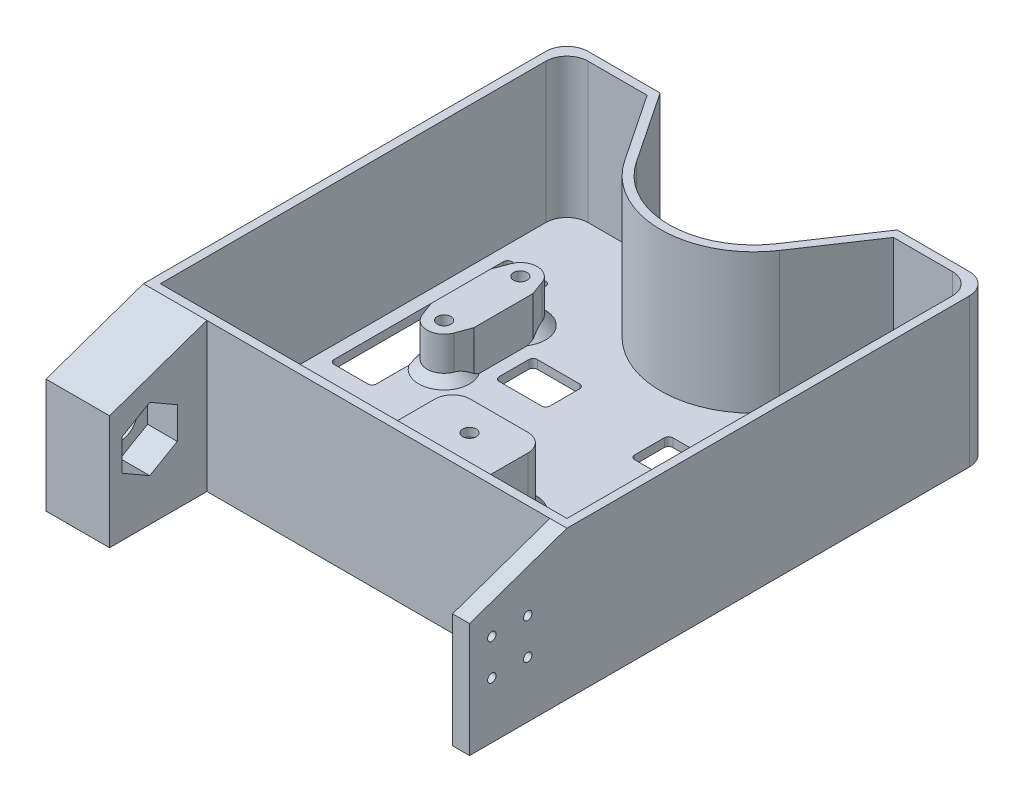
SolidWorks part; units mm, degrees
ref_plane "Ebene vorne" through (0, 0, 0) normal (0, 0, 1) x (1, 0, 0)
ref_plane "Ebene oben" through (0, 0, 0) normal (0, 1, 0) x (1, 0, 0)
ref_plane "Ebene rechts" through (0, 0, 0) normal (1, 0, 0) x (0, 0, -1)
sketch "Grundplatte" plane through (0, 0, 0) normal (0, 1, 0) x (1, 0, 0)
  line L0 (0, 69.0751) -> (0, -94.5087) construction
  line L2 (-50, 50) -> (-50, -50)
  line L3 (-50, -50) -> (50, -50)
  line L4 (50, 50) -> (50, -50)
  line L5 (-50, 50) -> (50, -50) construction
  line L6 (-50, -50) -> (50, 50) construction
  line L7 (-50, 50) -> (-28, 50)
  line L8 (-28, 50) -> (-16.6199, 33)
  line L9 (28, 50) -> (16.6199, 33)
  line L10 (50, 50) -> (28, 50)
  arc A0 (-16.6199, 33) -> (16.6199, 33) centre (0, 44.1257) ccw
  point P0 (0, 0)
  dimension "D4" = 20
  dimension "D1" = 100
  dimension "D2" = 100
  dimension "D3" = 22
  dimension "D5" = 17
extrude "Aufsatz-Linear austragen1" add sketch "Grundplatte" along normal blind 35
shell "Wandung1" thickness 2 removed face at (0, 35, -19.6407)
sketch "Skizze1" plane through (0, 2, 0) normal (0, 1, 0) x (1, 0, 0)
  line L0 (0, 51.8201) -> (0, -55.3816) construction
  line L1 (-28, 50) -> (-50, 50) construction
  line L2 (-45, 31) -> (-35, 31)
  line L3 (-45, 31) -> (-45, -11)
  line L4 (-45, -11) -> (-35, -11)
  line L5 (-35, 31) -> (-35, -11)
  line L6 (-45, 31) -> (-35, -11) construction
  line L7 (-45, -11) -> (-35, 31) construction
  line L8 (50, 50) -> (28, 50) construction
  line L9 (35, 31) -> (45, 31)
  line L10 (35, 31) -> (35, -11)
  line L11 (35, -11) -> (45, -11)
  line L12 (45, 31) -> (45, -11)
  line L13 (35, 31) -> (45, -11) construction
  line L14 (35, -11) -> (45, 31) construction
  point P3 (-40, 10)
  point P10 (40, 10)
  dimension "D1" = 10
  dimension "D2" = 42
  dimension "D3" = 40
  dimension "D4" = 40
  dimension "D5" = 42
  dimension "D6" = 10
  dimension "D7" = 40
  dimension "D8" = 40
extrude "Schnitt-Linear austragen1" cut sketch "Skizze1" against normal up to surface (2 mm away) up to face at (0, 0, -19.6407)
sketch "Skizze2" plane through (0, 2, 0) normal (0, 1, 0) x (1, 0, 0)
  line L20 (-65.457, 10) -> (65.6069, 10) construction
  line L21 (0, 51.8201) -> (0, -54.6693) construction
  line L22 (-35, -11) -> (-35, 31) construction
  line L24 (-35, 16) -> (-35, 4)
  line L26 (-25, 16) -> (-25, 4)
  line L27 (-35, 16) -> (-25, 4) construction
  line L28 (-35, 4) -> (-25, 16) construction
  line L33 (35, 16) -> (35, 17)
  line L34 (33.7533, 20.3831) -> (35, 17)
  line L36 (-35, 16) -> (-35, 17)
  line L37 (-25, 16) -> (-25, 17)
  line L38 (-35, 4) -> (-35, 3)
  line L39 (-25, 4) -> (-25, 3)
  line L40 (-26.2467, 20.3831) -> (-25, 17)
  line L41 (-33.7533, 20.3831) -> (-35, 17)
  line L42 (-26.2467, -0.3831) -> (-25, 3)
  line L43 (-33.7533, -0.3831) -> (-35, 3)
  line L44 (26.2467, 20.3831) -> (25, 17)
  line L45 (25, 16) -> (25, 17)
  line L46 (25, 16) -> (25, 4)
  line L47 (25, 4) -> (25, 3)
  line L48 (26.2467, -0.3831) -> (25, 3)
  line L49 (33.7533, -0.3831) -> (35, 3)
  line L50 (35, 4) -> (35, 3)
  line L51 (35, 16) -> (35, 4)
  circle A4 centre (-30, 19) radius 1.6
  circle A5 centre (-30, 1) radius 1.6
  arc A6 (-26.2467, 20.3831) -> (-33.7533, 20.3831) centre (-30, 19) ccw
  arc A7 (-26.2467, -0.3831) -> (-33.7533, -0.3831) centre (-30, 1) cw
  circle A8 centre (30, 1) radius 1.6
  circle A9 centre (30, 19) radius 1.6
  arc A10 (26.2467, 20.3831) -> (33.7533, 20.3831) centre (30, 19) cw
  arc A11 (26.2467, -0.3831) -> (33.7533, -0.3831) centre (30, 1) ccw
  point P4 (-30, 10)
  point P9 (30, 10)
  dimension "D9" = 3.2
  dimension "D10" = 3.2
  dimension "D13" = 4
  dimension "D14" = 4
  dimension "D2" = 30
  dimension "D3" = 10
  dimension "D5" = 1
  dimension "D6" = 1
  dimension "D7" = 1
  dimension "D8" = 1
  dimension "D11" = 9
  dimension "D12" = 9
extrude "Aufsatz-Linear austragen2" add sketch "Skizze2" along normal blind 10
fillet "Verrundung1" radius 1 8 edges at (35, 1, -31) (45, 1, -31) (35, 1, 11) (45, 1, 11) (-35, 1, 11) (-45, 1, 11) (-45, 1, -31) (-35, 1, -31)
sketch "Skizze6" plane through (0, 12, 0) normal (0, 1, 0) x (1, 0, 0)
  circle A0 centre (-30, 19) radius 1.6
  circle A1 centre (-30, 1) radius 1.6
  circle A2 centre (30, 19) radius 1.6
  circle A3 centre (30, 1) radius 1.6
  dimension "D1" = 3.2
  dimension "D2" = 3.2
  dimension "D3" = 3.2
  dimension "D4" = 3.2
extrude "Schnitt-Linear austragen2" cut sketch "Skizze6" against normal through all
sketch "Skizze7" plane through (0, 0, 0) normal (0, -1, 0) x (1, 0, 0)
  line L0 (0, 58.5427) -> (0, -57.727) construction
  line L1 (-26.7091, -1) -> (-28.3546, 1.85)
  line L2 (-28.3546, 1.85) -> (-31.6454, 1.85)
  line L3 (-31.6454, 1.85) -> (-33.2909, -1)
  line L4 (-33.2909, -1) -> (-31.6454, -3.85)
  line L5 (-31.6454, -3.85) -> (-28.3546, -3.85)
  line L6 (-28.3546, -3.85) -> (-26.7091, -1)
  line L7 (28.3546, -21.85) -> (26.7091, -19)
  line L8 (-26.7091, -19) -> (-28.3546, -16.15)
  line L9 (-28.3546, -16.15) -> (-31.6454, -16.15)
  line L10 (-31.6454, -16.15) -> (-33.2909, -19)
  line L11 (-33.2909, -19) -> (-31.6454, -21.85)
  line L12 (-31.6454, -21.85) -> (-28.3546, -21.85)
  line L13 (-28.3546, -21.85) -> (-26.7091, -19)
  line L14 (31.6454, -21.85) -> (28.3546, -21.85)
  line L15 (33.2909, -19) -> (31.6454, -21.85)
  line L16 (31.6454, -16.15) -> (33.2909, -19)
  line L17 (28.3546, -16.15) -> (31.6454, -16.15)
  line L18 (26.7091, -19) -> (28.3546, -16.15)
  line L19 (28.3546, -3.85) -> (26.7091, -1)
  line L20 (31.6454, -3.85) -> (28.3546, -3.85)
  line L21 (33.2909, -1) -> (31.6454, -3.85)
  line L22 (31.6454, 1.85) -> (33.2909, -1)
  line L23 (28.3546, 1.85) -> (31.6454, 1.85)
  line L24 (26.7091, -1) -> (28.3546, 1.85)
  circle A0 centre (-30, -1) radius 2.85 construction
  circle A1 centre (-30, -19) radius 2.85 construction
  dimension "D1" = 5.7
  dimension "D2" = 5.7
extrude "Schnitt-Linear austragen3" cut sketch "Skizze7" against normal offset from surface (9 mm away) 3 up to face at (30, 12, -2.6)
chamfer "Fase1" distance 2 angle 45 8 edges at (34.3766, 2, -1.3084) (30, 2, 3) (34.3766, 2, -18.6916) (30, 2, -23) (-34.3766, 2, -18.6916) (-30, 2, -23) (-34.3766, 2, -1.3084) (-30, 2, 3)
sketch "Skizze8" plane through (0, 0, 0) normal (0, -1, 0) x (1, 0, 0)
  line L0 (0, 60.6503) -> (0, -60.3099) construction
  line L1 (22, -5) -> (10, -5)
  line L2 (-22, -14) -> (-10, -14)
  line L3 (-22, -14) -> (-22, -5)
  line L4 (-22, -5) -> (-10, -5)
  line L5 (-10, -14) -> (-10, -5)
  line L10 (10, -14) -> (10, -5)
  line L11 (22, -14) -> (10, -14)
  line L12 (22, -14) -> (22, -5)
  circle A0 centre (-30, -1) radius 1.6 construction
  dimension "D2" = 4
  dimension "D1" = 12
  dimension "D3" = 10
  dimension "D4" = 9
extrude "Schnitt-Linear austragen4" cut sketch "Skizze8" against normal up to surface (2 mm away) up to face at (-36.1139, 2, -10)
fillet "Verrundung2" radius 1 8 edges at (-22, 1, -14) (-22, 1, -5) (-10, 1, -5) (-10, 1, -14) (22, 1, -14) (22, 1, -5) (10, 1, -14) (10, 1, -5)
fillet "Verrundung3" radius 5 2 edges at (-50, 17.5, -50) (50, 17.5, -50)
fillet "Verrundung4" radius 5 2 edges at (48, 18.5, -48) (-48, 18.5, -48)
sketch "Skizze9" plane through (0, 0, 0) normal (0, -1, 0) x (1, 0, 0)
  line L0 (0, 55.7734) -> (0, -61.0444) construction
  line L1 (-11, -5) -> (-21, -5) construction
  line L2 (-6.8, 43) -> (6.8, 43)
  line L3 (-8, 41.8) -> (-8, 20.2)
  line L4 (-6.8, 19) -> (6.8, 19)
  line L5 (8, 41.8) -> (8, 20.2)
  line L6 (-8, 43) -> (8, 19) construction
  line L7 (-8, 19) -> (8, 43) construction
  arc A0 (6.8, 19) -> (8, 20.2) centre (6.8, 20.2) ccw
  arc A1 (-8, 20.2) -> (-6.8, 19) centre (-6.8, 20.2) ccw
  arc A2 (-6.8, 43) -> (-8, 41.8) centre (-6.8, 41.8) ccw
  arc A3 (6.8, 43) -> (8, 41.8) centre (6.8, 41.8) cw
  point P3 (0, 31)
  dimension "D4" = 1.2
  dimension "D1" = 24
  dimension "D2" = 16
  dimension "D3" = 36
extrude "Schnitt-Linear austragen5" cut sketch "Skizze9" against normal up to next
sketch "Skizze11" plane through (0, 2, 0) normal (0, 1, 0) x (1, 0, 0)
  line L25 (-6.8, -46) -> (6.8, -46)
  line L26 (-11, -20.2) -> (-11, -41.8)
  line L27 (11, -41.8) -> (11, -20.2)
  line L28 (6.8, -16) -> (-6.8, -16)
  line L29 (-6.8, -46) -> (6.8, -46)
  line L30 (-11, -20.2) -> (-11, -41.8)
  line L31 (11, -41.8) -> (11, -20.2)
  line L32 (6.8, -16) -> (-6.8, -16)
  line L62 (-8, -20.2) -> (-8, -41.8)
  line L63 (-6.8, -43) -> (6.8, -43)
  line L64 (8, -41.8) -> (8, -20.2)
  line L65 (-6.8, -19) -> (6.8, -19)
  arc A19 (6.8, -46) -> (11, -41.8) centre (6.8, -41.8) ccw
  arc A20 (-11, -41.8) -> (-6.8, -46) centre (-6.8, -41.8) ccw
  arc A21 (-6.8, -16) -> (-11, -20.2) centre (-6.8, -20.2) ccw
  arc A22 (11, -20.2) -> (6.8, -16) centre (6.8, -20.2) ccw
  arc A23 (6.8, -46) -> (11, -41.8) centre (6.8, -41.8) ccw
  arc A24 (-11, -41.8) -> (-6.8, -46) centre (-6.8, -41.8) ccw
  arc A25 (-6.8, -16) -> (-11, -20.2) centre (-6.8, -20.2) ccw
  arc A26 (11, -20.2) -> (6.8, -16) centre (6.8, -20.2) ccw
  arc A50 (-6.8, -19) -> (-8, -20.2) centre (-6.8, -20.2) ccw
  arc A51 (6.8, -19) -> (8, -20.2) centre (6.8, -20.2) cw
  arc A52 (-6.8, -43) -> (-8, -41.8) centre (-6.8, -41.8) cw
  arc A53 (6.8, -43) -> (8, -41.8) centre (6.8, -41.8) ccw
  dimension "D1" = 3
extrude "Aufsatz-Linear austragen3" add sketch "Skizze11" along normal blind 12
sketch "Skizze12" plane through (0, 14, 0) normal (0, 1, 0) x (1, 0, 0)
  line L30 (11, -41.8) -> (11, -20.2)
  line L31 (-6.8, -46) -> (6.8, -46)
  line L32 (-11, -20.2) -> (-11, -41.8)
  line L33 (6.8, -16) -> (-6.8, -16)
  line L34 (11, -41.8) -> (11, -20.2)
  line L35 (-6.8, -46) -> (6.8, -46)
  line L36 (-11, -20.2) -> (-11, -41.8)
  line L37 (6.8, -16) -> (-6.8, -16)
  arc A14 (6.8, -46) -> (11, -41.8) centre (6.8, -41.8) ccw
  arc A15 (-11, -41.8) -> (-6.8, -46) centre (-6.8, -41.8) ccw
  arc A16 (-6.8, -16) -> (-11, -20.2) centre (-6.8, -20.2) ccw
  arc A17 (11, -20.2) -> (6.8, -16) centre (6.8, -20.2) ccw
  arc A18 (6.8, -46) -> (11, -41.8) centre (6.8, -41.8) ccw
  arc A19 (-11, -41.8) -> (-6.8, -46) centre (-6.8, -41.8) ccw
  arc A20 (-6.8, -16) -> (-11, -20.2) centre (-6.8, -20.2) ccw
  arc A21 (11, -20.2) -> (6.8, -16) centre (6.8, -20.2) ccw
  dimension "D1" = 3
extrude "Aufsatz-Linear austragen4" add sketch "Skizze12" along normal blind 2
chamfer "Fase2" distance 2 angle 45 8 edges at (-11, 2, 31) (-9.7698, 2, 44.7698) (-9.7698, 2, 17.2302) (0, 2, 46) (0, 2, 16) (9.7698, 2, 44.7698) (9.7698, 2, 17.2302) (11, 2, 31)
sketch "Skizze13" plane through (0, 16, 0) normal (0, 1, 0) x (1, 0, 0)
  line L0 (0, 40.7845) -> (0, -65.4996) construction
  line L1 (-15.9895, -31) -> (16.789, -31) construction
  line L2 (6.8, -16) -> (-6.8, -16) construction
  line L3 (-6.8, -46) -> (6.8, -46) construction
  circle A0 centre (0, -23) radius 1.6
  circle A1 centre (0, -39) radius 1.6
  dimension "D1" = 3.2
  dimension "D2" = 3.2
  dimension "D3" = 16
extrude "Schnitt-Linear austragen6" cut sketch "Skizze13" along direction (0, 1, 0) on the side against the normal up to surface (2 mm away) up to face at (0, 14, 31)
sketch "Skizze14" plane through (0, 0, 50) normal (0, 0, 1) x (1, 0, 0)
  line L0 (0, 49.837) -> (0, -24.1023) construction
  line L1 (-50, 35) -> (-50, 0)
  line L2 (-50, 0) -> (-35, 0)
  line L3 (-50, 0) -> (50, 0) construction
  line L4 (-35, 0) -> (-35, 35)
  line L5 (-50, 35) -> (50, 35) construction
  line L6 (-35, 35) -> (-50, 35)
  line L7 (50, 35) -> (46, 35)
  line L8 (46, 35) -> (46, 0)
  line L9 (46, 0) -> (50, 0)
  line L10 (50, 0) -> (50, 35)
  dimension "D1" = 15
  dimension "D2" = 4
extrude "Aufsatz-Linear austragen5" add sketch "Skizze14" along normal blind 23
sketch "Skizze18" plane through (50, 0, 0) normal (1, 0, 0) x (0, 0, -1)
  line L0 (-50, 46.4423) -> (-50, -7.8316) construction
  line L1 (-73, 0) -> (-73, 35) construction
  line L3 (-73, 0) -> (45, 0) construction
  circle A0 centre (-63.5, 17.5) radius 6 construction
  circle A2 centre (-59.2574, 13.2574) radius 1
  circle A4 centre (-67.7426, 13.2574) radius 1
  circle A6 centre (-67.7426, 21.7426) radius 1
  circle A8 centre (-59.2574, 21.7426) radius 1
  point P27 (-63.5, 17.5)
  dimension "D2" = 12
  dimension "D5" = 2
  dimension "D6" = 2
  dimension "D7" = 2
  dimension "D8" = 2
  dimension "D1" = 23
  dimension "D3" = 13.5
  dimension "D4" = 17.5
extrude "Schnitt-Linear austragen8" cut sketch "Skizze18" against normal up to surface (4 mm away) up to face at (46, 17.5, 61.5)
sketch "Skizze19" plane through (46, 0, 0) normal (-1, 0, 0) x (0, 0, 1)
  line L0 (50, 40.9842) -> (50, -6.1788) construction
  line L1 (73, 35) -> (73, 0) construction
  line L2 (73, 35) -> (50, 35) construction
  circle A0 centre (63.5, 17.5) radius 2.5
  dimension "D2" = 5
  dimension "D1" = 23
  dimension "D3" = 13.5
  dimension "D4" = 17.5
extrude "Schnitt-Linear austragen9" cut sketch "Skizze19" against normal blind 2.5
sketch "Skizze20" plane through (0, 0, 50) normal (0, 0, 1) x (1, 0, 0)
  line L0 (46, 35) -> (46, 0) construction
  line L1 (41, 22.5) -> (46, 22.5)
  line L2 (41, 22.5) -> (41, 12.5)
  line L3 (41, 12.5) -> (46, 12.5)
  line L4 (46, 22.5) -> (46, 12.5)
  line L5 (41, 22.5) -> (46, 12.5) construction
  line L6 (41, 12.5) -> (46, 22.5) construction
  line L7 (-35, 35) -> (46, 35) construction
  point P0 (43.5, 17.5)
  dimension "D1" = 10
  dimension "D2" = 5
  dimension "D3" = 17.5
extrude "Schnitt-Linear austragen10" cut sketch "Skizze20" against normal up to surface (2 mm away) up to face at (0, 13, 48)
sketch "Skizze21" plane through (-50, 0, 0) normal (-1, 0, 0) x (0, 0, 1)
  line L0 (50, 45.8781) -> (50, -12.9091) construction
  line L1 (73, 35) -> (73, 0) construction
  line L2 (-45, 35) -> (73, 35) construction
  circle A0 centre (63.5, 17.5) radius 4
  dimension "D4" = 8
  dimension "D1" = 23
  dimension "D2" = 13.5
  dimension "D3" = 17.5
extrude "Schnitt-Linear austragen11" cut sketch "Skizze21" against normal up to surface (15 mm away) contours A0 up to face at (-35, 17.5, 61.5)
sketch "Skizze23" plane through (-50, 0, 0) normal (-1, 0, 0) x (0, 0, 1)
  circle A0 centre (63.5, 17.5) radius 7.5
  dimension "D1" = 15
extrude "Schnitt-Linear austragen12" cut sketch "Skizze23" against normal blind 1
sketch "Skizze24" plane through (-49, 0, 0) normal (-1, 0, 0) x (0, 0, 1)
  circle A0 centre (63.5, 17.5) radius 7.5
  dimension "D1" = 15
extrude "Schnitt-Linear austragen13" cut sketch "Skizze24" against normal blind 4 draft 45
sketch "Skizze26" plane through (-35, 0, 0) normal (1, 0, 0) x (0, 0, -1)
  line L0 (-73, 0) -> (-73, 35) construction
  line L1 (-57, 13.7472) -> (-57, 21.2528)
  line L2 (-57, 21.2528) -> (-63.5, 25.0056)
  line L3 (-63.5, 25.0056) -> (-70, 21.2528)
  line L4 (-70, 21.2528) -> (-70, 13.7472)
  line L5 (-70, 13.7472) -> (-63.5, 9.9944)
  line L6 (-63.5, 9.9944) -> (-57, 13.7472)
  circle A0 centre (-63.5, 17.5) radius 6.5 construction
  dimension "D1" = 13
extrude "Schnitt-Linear austragen14" cut sketch "Skizze26" against normal blind 7
sketch "Skizze29" plane through (-50, 0, 0) normal (-1, 0, 0) x (0, 0, 1)
  line L0 (50, 41.4433) -> (50, -3.8482) construction
  line L1 (73, 35) -> (73, 0) construction
  line L2 (73, 35) -> (73, 27)
  line L3 (73, 27) -> (50, 35)
  line L4 (50, 35) -> (73, 35)
  dimension "D1" = 23
  dimension "D2" = 8
extrude "Schnitt-Linear austragen15" cut sketch "Skizze29" against normal up to surface (100 mm away) up to face at (50, 21.7426, 58.2574)
